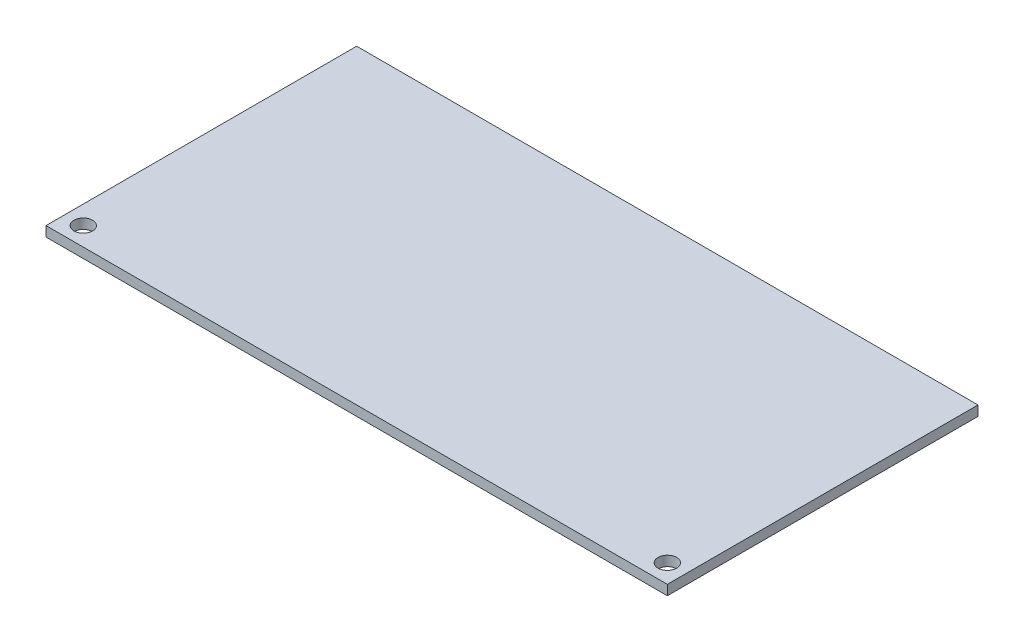
SolidWorks part; units mm, degrees
ref_plane "Front Plane" through (0, 0, 0) normal (0, 0, 1) x (1, 0, 0)
ref_plane "Top Plane" through (0, 0, 0) normal (0, 1, 0) x (1, 0, 0)
ref_plane "Right Plane" through (0, 0, 0) normal (1, 0, 0) x (0, 0, -1)
sketch "Sketch1" plane through (0, 0, 0) normal (0, 1, 0) x (1, 0, 0)
  line L1 (0, 0) -> (100, 0)
  line L2 (0, 0) -> (0, 50)
  line L3 (0, 50) -> (100, 50)
  line L4 (100, 0) -> (100, 50)
  dimension "D1" = 50
  dimension "D2" = 100
extrude "Boss-Extrude1" add sketch "Sketch1" along normal blind 1.6
sketch "Sketch2" plane through (0, 1.6, 0) normal (0, 1, 0) x (1, 0, 0)
  line L0 (0, 0) -> (100, 0) construction
  line L1 (0, 50) -> (0, 0) construction
  line L2 (100, 0) -> (100, 50) construction
  circle A0 centre (3, 3) radius 1.5
  circle A1 centre (97, 3) radius 1.5
  dimension "D1" = 3
  dimension "D2" = 3
  dimension "D3" = 3
  dimension "D4" = 3
extrude "Cut-Extrude1" cut sketch "Sketch2" against normal up to next
